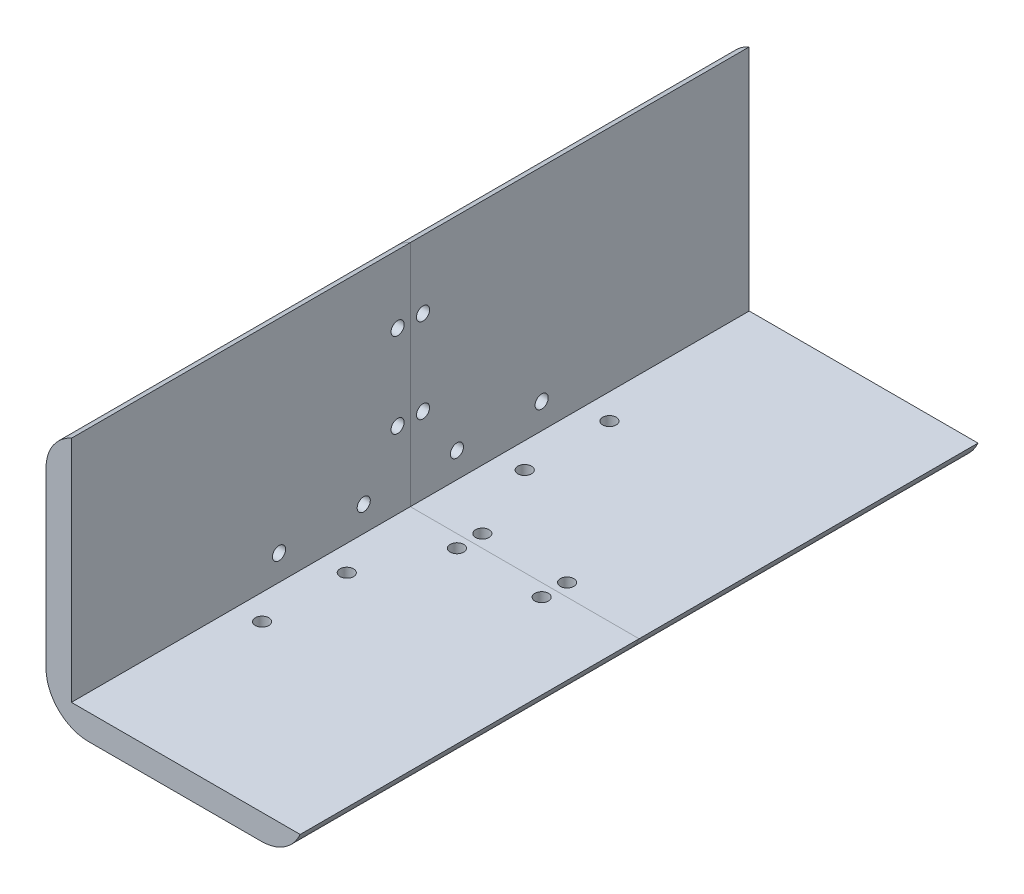
SolidWorks part; units mm, degrees
ref_plane "前视基准面" through (0, 0, 0) normal (0, 0, 1) x (1, 0, 0)
ref_plane "上视基准面" through (0, 0, 0) normal (0, 1, 0) x (1, 0, 0)
ref_plane "右视基准面" through (0, 0, 0) normal (1, 0, 0) x (0, 0, -1)
other "Configuration Table"
sketch "草图1" plane through (0, 0, 0) normal (0, 0, 1) x (1, 0, 0)
  line L0 (0, 0) -> (0, 60)
  line L1 (0, 60) -> (6, 60)
  line L2 (6, 60) -> (6, 6)
  line L3 (6, 6) -> (60, 6)
  line L4 (60, 6) -> (60, 0)
  line L5 (60, 0) -> (0, 0)
  dimension "D1" = 6
  dimension "D2" = 6
  dimension "D3" = 60
  dimension "D4" = 60
extrude "凸台-拉伸1" add sketch "草图1" along normal mid plane 80
fillet "圆角1" radius 10 3 edges at (0, 60, 0) (60, 0, 0) (0, 0, 0)
sketch "草图3" plane through (0, 0, 0) normal (-1, 0, 0) x (0, 0, 1)
  line L0 (-29, 12) -> (-9, 12) construction
  line L1 (40, 0) -> (-40, 0) construction
  line L2 (-40, 50.8348) -> (-40, 10) construction
  circle A0 centre (-37, 44) radius 1.55
  circle A1 centre (-37, 24) radius 1.55
  circle A2 centre (-29, 12) radius 1.55
  circle A3 centre (-9, 12) radius 1.55
  dimension "D1" = 3.1
  dimension "D7" = 11
  dimension "D2" = 20
  dimension "D3" = 44
  dimension "D4" = 3
  dimension "D5" = 20
  dimension "D6" = 12
extrude "切除-拉伸1" cut sketch "草图3" against normal through all
sketch "草图4" plane through (0, 6, 0) normal (0, 1, 0) x (1, 0, 0)
  line L0 (12, 19) -> (12, -1) construction
  line L1 (60, 40) -> (6, 40) construction
  circle A0 centre (12, -1) radius 1.6
  circle A1 centre (12, 19) radius 1.6
  dimension "D1" = 12
  dimension "D3" = 3.2
  dimension "D2" = 21
  dimension "D4" = 20
extrude "切除-拉伸2" cut sketch "草图4" against normal through all
sketch "草图5" plane through (0, 0, 0) normal (0, -1, 0) x (1, 0, 0)
  line L0 (20, -37) -> (40, -37) construction
  line L1 (10, -40) -> (50.8348, -40) construction
  line L2 (6, 40) -> (6, -40) construction
  circle A0 centre (20, -37) radius 1.6
  circle A1 centre (40, -37) radius 1.6
  dimension "D1" = 3.2
  dimension "D2" = 3
  dimension "D3" = 20
  dimension "D4" = 14
extrude "切除-拉伸3" cut sketch "草图5" against normal through all
mirror "镜向1" about plane through (0, 0, -40) normal (0, 0, -1) of bodies 109
